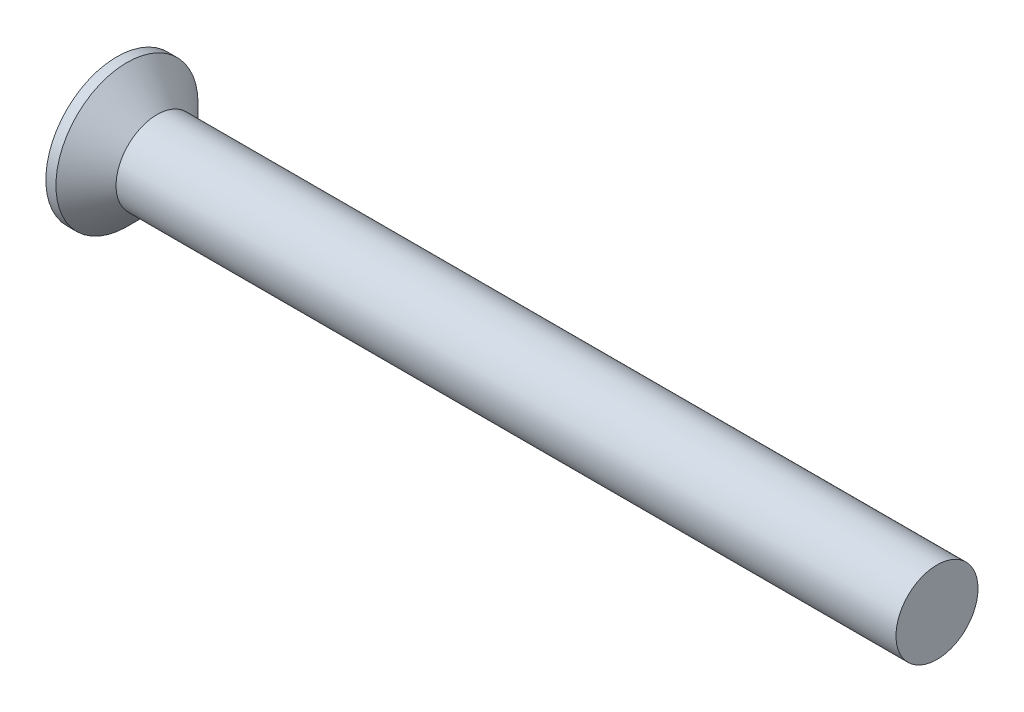
SolidWorks part; units mm, degrees
ref_plane "Front" through (0, 0, 0) normal (0, 0, 1) x (1, 0, 0)
ref_plane "Top" through (0, 0, 0) normal (0, 1, 0) x (1, 0, 0)
ref_plane "Right" through (0, 0, 0) normal (1, 0, 0) x (0, 0, -1)
sketch "Sketch1" plane through (0, 0, 0) normal (0, 0, 1) x (1, 0, 0)
  line L0 (30, 1.5) -> (2.7379, 1.5)
  line L1 (2.7379, 1.5) -> (2.4674, 1.2295) construction
  line L2 (1.65, 1.3174) -> (1.4674, 1.5) construction
  line L3 (0.3674, 2.6) -> (0, 2.6)
  line L4 (30, 1.5) -> (30, 0)
  line L5 (4.5158, 0) -> (-89.8219, 0) construction
  line L6 (30, 0) -> (0, 0)
  line L7 (0, 2.6) -> (0, 0)
  line L8 (1.8621, 1.2295) -> (2.4674, 1.2295) construction
  line L9 (2.7379, 1.5) -> (1.4674, 1.5)
  line L10 (1.4674, 1.5) -> (0.3674, 2.6)
  arc A0 (1.8621, 1.2295) -> (1.65, 1.3174) centre (1.8621, 1.5295) cw construction
  point P11 (1.7379, 1.2295)
  dimension "D1" = 45
  dimension "dk" = 5.2
  dimension "l" = 30
  dimension "a" = 1
  dimension "D3" = 45
  dimension "k" = 1.65
revolve "Base" add sketch "Sketch1" angle 360 about L5
cosmetic thread "ThreadCosmetic1" [suppressed] parameters "bb"=28.35
dome "BaseTop" faces to dome 1 distance 0.7 reverse direction no elliptical dome no face at (0, 0, -2.6) parameters "f"=0.7
ref_plane "Plane1" through (-0.7, 0, 0) normal (1, 0, 0) x (0, 0, -1)
sketch "Sketch6" plane through (-0.7, 0, 0) normal (-1, 0, 0) x (0, 0, 1)
  line L0 (-1.9271, 0) -> (2.0512, 0) construction
  line L1 (0, 1.8651) -> (0, -2.0207) construction
  line L2 (0.34, 0.34) -> (0.34, 1.7)
  line L3 (0.34, 1.7) -> (-0.34, 1.7)
  line L4 (-0.34, 0.34) -> (-0.34, 1.7)
  line L5 (0.34, 0.34) -> (1.7, 0.34)
  line L6 (1.7, 0.34) -> (1.7, -0.34)
  line L7 (-1.7, 0.34) -> (-1.7, -0.34)
  line L8 (-0.34, 0.34) -> (-1.7, 0.34)
  line L9 (-0.34, -0.34) -> (-1.7, -0.34)
  line L10 (0.34, -0.34) -> (1.7, -0.34)
  line L11 (-0.34, -0.34) -> (-0.34, -1.7)
  line L12 (0.34, -1.7) -> (-0.34, -1.7)
  line L13 (0.34, -0.34) -> (0.34, -1.7)
  point P16 (-1.7, 0)
  point P17 (1.7, 0)
extrude "CrossRecess" cut sketch "Sketch6" against normal blind 0.825
draft "Draft9" type of draft neutral plane draft angle 30 neutral plane "Plane1" faces to draft 4 face at (-0.141, 0, -1.7) face at (-0.141, -1.7, 0) face at (-0.141, 0, 1.7) face at (-0.141, 1.7, 0) neutral plane through (-0.7, 0, 0) neutral plane normal (1, 0, 0) reverse direction yes parameters "D1"=30
fillet "Fillet5" radius 0.3 4 edges at (-0.2763, -0.34, 0.34) (-0.2763, -0.34, -0.34) (-0.2763, 0.34, -0.34) (-0.2763, 0.34, 0.34)
sketch "Sketch7" plane through (-0.7, 0, 0) normal (-1, 0, 0) x (0, 0, 1)
  line L0 (-2.0126, 0) -> (1.9757, 0) construction
  line L1 (0, 1.9314) -> (0, -2.0126) construction
  line L2 (0, 0) -> (1.5555, 1.5555) construction
  line L3 (0, 0.5081) -> (1.2021, 1.2021)
  line L4 (-1.5402, 1.5402) -> (0, 0) construction
  line L5 (0.5081, 0) -> (1.2021, 1.2021)
  line L6 (0, -0.5081) -> (1.2021, -1.2021)
  line L7 (0.5081, 0) -> (1.2021, -1.2021)
  line L8 (-0.5081, 0) -> (-1.2021, -1.2021)
  line L9 (0, -0.5081) -> (-1.2021, -1.2021)
  line L10 (-0.5081, 0) -> (-1.2021, 1.2021)
  line L11 (0, 0.5081) -> (-1.2021, 1.2021)
  dimension "D3" = 15
extrude "Cut-Extrude3" [suppressed] cut sketch "Sketch7" against normal blind 10 draft 20
sketch "Sketch8" plane through (0, 0, 0) normal (0, 0, 1) x (1, 0, 0)
  line L0 (5, 1.5) -> (3.75, 1.2295)
  line L1 (3.75, 1.2295) -> (1.7379, 1.2295)
  line L3 (30, -1.5) -> (30, 1.5) construction
  line L4 (1.8621, 1.2295) -> (2.4674, 1.2295) construction
  line L5 (1.8458, 1.1216) -> (1.7379, 1.2295)
  line L6 (1.8458, 1.1216) -> (1.8458, 6.2295)
  line L7 (1.8458, 6.2295) -> (5, 6.2295)
  line L8 (5, 6.2295) -> (5, 1.5)
  line L9 (62.4753, 0) -> (52.9594, 0) construction
  line L10 (1.65, 1.3174) -> (1.4674, 1.5) construction
  dimension "D1" = 5
  dimension "x" = 1.25
sketch "Sketch9" plane through (0, 0, 0) normal (0, 0, 1) x (1, 0, 0)
  line L0 (30, 1.2657) -> (30.1352, 1.5)
  line L1 (30.1352, 1.5) -> (30.1352, 1.7705)
  line L2 (30.1352, 1.7705) -> (29.8647, 1.7705)
  line L3 (29.8647, 1.7705) -> (29.8647, 1.5)
  line L4 (29.8647, 1.5) -> (30, 1.2657)
  line L5 (30, -1.5) -> (30, 1.5) construction
  line L6 (0, 0) -> (66.6901, 0) construction
  dimension "D2" = 0.2705
revolve "Cut-Revolve10" [suppressed] cut sketch "Sketch9" angle 360 about L6
pattern_linear "LPattern10" [suppressed] count 87 spacing 0.3246 along (-1, 0, 0) of bodies 105
equation "\"D1@Sketch6\" = \"m@Sketch6\" / 5"
equation "\"D1@CrossRecess\" = \"k@Sketch1\" / 2"
equation "\"D1@Plane1\" = \"f@BaseTop\""
equation "\"D1@Sketch9\" = \"d@Sketch1\""
equation "\"D2@Sketch9\" =  ( \"d@Sketch1\" - \"THD_MINOR@ThreadCosmetic1\" )  / 2"
equation "\"D3@LPattern10\" = \"D2@Sketch9\" * 1.2"
equation "\"D1@LPattern10\" = \"bb@ThreadCosmetic1\" / \"D3@LPattern10\" "
